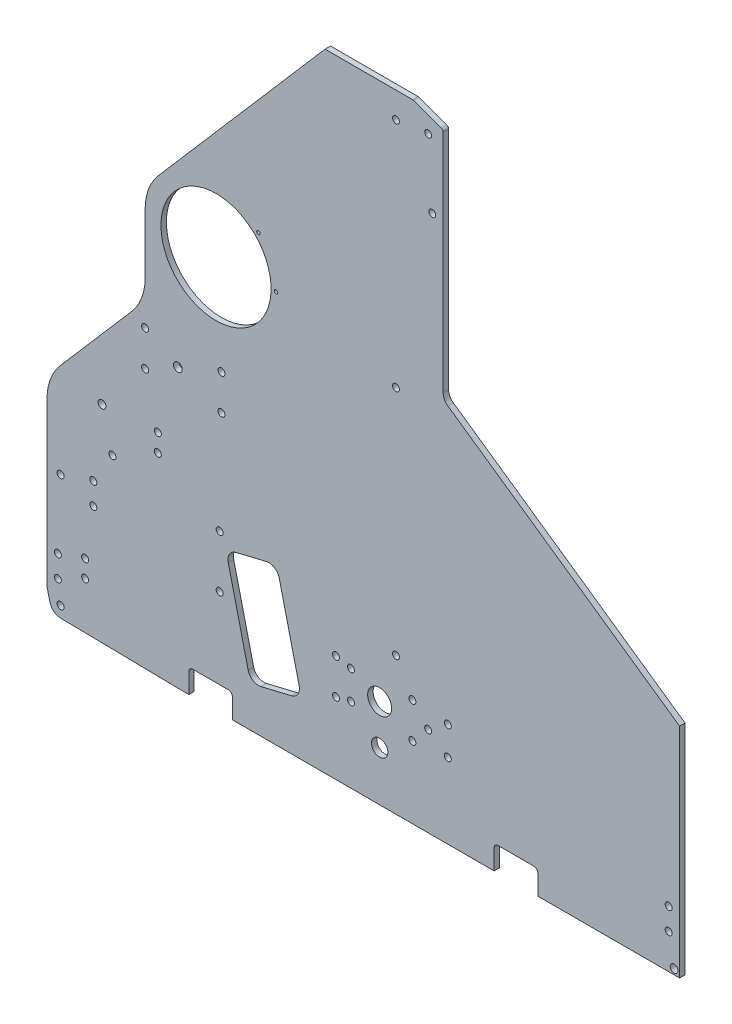
SolidWorks part; units mm, degrees
ref_plane "Front Plane" through (0, 0, 0) normal (0, 0, 1) x (1, 0, 0)
ref_plane "Top Plane" through (0, 0, 0) normal (0, 1, 0) x (1, 0, 0)
ref_plane "Right Plane" through (0, 0, 0) normal (1, 0, 0) x (0, 0, -1)
sketch "Sketch1" plane through (0, 0, 0) normal (0, 0, 1) x (1, 0, 0)
  line L0 (82.55, -20.32) -> (82.55, -6.35)
  line L2 (0, 0) -> (0, 157.48)
  line L4 (368.3, -20.32) -> (368.3, 106.68)
  line L5 (82.55, -6.35) -> (107.95, -6.35)
  line L6 (107.95, -6.35) -> (107.95, -20.32)
  line L7 (107.95, -20.32) -> (260.35, -20.32)
  line L8 (260.35, -20.32) -> (260.35, -6.35)
  line L9 (260.35, -6.35) -> (285.75, -6.35)
  line L10 (285.75, -6.35) -> (285.75, -20.32)
  line L11 (285.75, -20.32) -> (368.3, -20.32)
  line L12 (361.95, 12.7) -> (368.3, 12.7) construction
  line L13 (0, 0) -> (6.35, 0) construction
  line L14 (0.1896, -7.8901) -> (1.7771, -14.2401)
  line L15 (7.8295, -19.0491) -> (82.55, -20.32)
  line L16 (0, 0) -> (0, -6.35)
  line L17 (76.2, 141.605) -> (79.375, 141.605) construction
  line L18 (57.15, 131.2863) -> (101.6, 131.2862) construction
  line L19 (57.15, 131.2863) -> (57.15, 151.9238) construction
  line L20 (101.6, 131.2862) -> (101.6, 151.9237) construction
  line L21 (57.15, 151.9238) -> (101.6, 151.9237) construction
  line L22 (57.15, 131.2863) -> (101.6, 151.9237) construction
  line L23 (101.6, 131.2862) -> (57.15, 151.9238) construction
  line L25 (203.2, 59.805) -> (203.2, 194.805) construction
  line L26 (203.2, 194.805) -> (203.2, 329.805) construction
  line L27 (355.6, 332.105) -> (330.2, 332.105) construction
  line L28 (330.2, 332.105) -> (330.2, 217.805) construction
  line L29 (330.2, 217.805) -> (355.6, 217.805) construction
  line L30 (355.6, 217.805) -> (355.6, 332.105) construction
  line L31 (203.2, 344.805) -> (203.2, 194.805) construction
  line L32 (50.8, 332.105) -> (76.2, 332.105) construction
  line L33 (76.2, 332.105) -> (76.2, 217.805) construction
  line L34 (50.8, 217.805) -> (50.8, 332.105) construction
  line L35 (76.2, 217.805) -> (50.8, 217.805) construction
  line L36 (213.2, 344.805) -> (230.6638, 338.455)
  line L37 (203.2, 344.805) -> (161.925, 344.805)
  line L38 (203.2, 344.805) -> (213.2, 344.805)
  line L39 (348.5362, 344.805) -> (413.4623, 344.805)
  line L40 (348.5362, 344.805) -> (230.6638, 344.805) construction
  line L42 (161.925, 344.805) -> (0, 157.48)
  line L44 (230.6638, 338.455) -> (230.6638, 202.565)
  line L45 (230.6638, 202.565) -> (368.3, 106.68)
  line L46 (213.2, 344.805) -> (-141.0713, 344.805) construction
  circle A0 centre (6.35, 0) radius 2.032
  circle A1 centre (6.35, 12.7) radius 2.032
  circle A2 centre (361.95, 0) radius 2.032
  circle A3 centre (361.95, 12.7) radius 2.032
  arc A5 (1.7771, -14.2401) -> (7.8295, -19.0491) centre (7.9375, -12.7) ccw
  circle A6 centre (7.9375, -12.7) radius 2.032
  arc A7 (0, -6.35) -> (0.1896, -7.8901) centre (6.35, -6.35) ccw
  circle A8 centre (38.1, 78.105) radius 2.032
  circle A9 centre (76.2, 141.605) radius 2.54
  circle A10 centre (101.6, 131.2862) radius 2.032
  circle A11 centre (101.6, 151.9237) radius 2.032
  circle A12 centre (57.15, 151.9238) radius 2.032
  circle A13 centre (57.15, 131.2863) radius 2.032
  circle A15 centre (203.2, 59.805) radius 2
  circle A16 centre (203.2, 194.805) radius 2
  circle A17 centre (203.2, 329.805) radius 2
  circle A18 centre (63.5, 313.055) radius 2.032
  circle A20 centre (355.6, 332.105) radius 2.032
  circle A21 centre (330.2, 332.105) radius 2.032
  circle A22 centre (355.6, 217.805) radius 2.032
  circle A23 centre (330.2, 217.805) radius 2.032
  circle A24 centre (50.8, 332.105) radius 2.032
  circle A25 centre (76.2, 332.105) radius 2.032
  circle A26 centre (50.8, 217.805) radius 2.032
  circle A27 centre (76.2, 217.805) radius 2.032
  circle A28 centre (221.9319, 332.105) radius 2
  circle A29 centre (224.3138, 293.243) radius 2.032
  point P82 (203.2, 344.805)
  point P83 (221.9319, 341.63)
  dimension "D6" = 4.064
  dimension "D10" = 6.35
  dimension "D11" = 4.064
  dimension "D17" = 38.1
  dimension "D27" = 4
  dimension "D31" = 4.064
  dimension "D32" = 41.275
  dimension "D36" = 4.064
  dimension "D47" = 45.212
  dimension "D48" = 4.064
  dimension "D25" = 5.08
  dimension "D2" = 127
  dimension "D3" = 13.97
  dimension "D4" = 25.4
  dimension "D5" = 152.4
  dimension "D7" = 12.7
  dimension "D8" = 6.35
  dimension "D9" = 20.32
  dimension "D12" = 12.7
  dimension "D13" = 1.5875
  dimension "D14" = 82.55
  dimension "D15" = 368.3
  dimension "D16" = 6.35
  dimension "D18" = 98.425
  dimension "D19" = 38.1
  dimension "D20" = 63.5
  dimension "D21" = 3.175
  dimension "D22" = 270
  dimension "D23" = 20.6375
  dimension "D24" = 44.45
  dimension "D28" = 135
  dimension "D29" = 12.7
  dimension "D30" = 15
  dimension "D33" = 63.5
  dimension "D34" = 27.4638
  dimension "D37" = 114.3
  dimension "D38" = 25.4
  dimension "D39" = 12.7
  dimension "D40" = 157.48
  dimension "D41" = 142.24
  dimension "D42" = 365.125
  dimension "D43" = 10
  dimension "D44" = 6.35
  dimension "D45" = 31.75
  dimension "D46" = 6.35
  dimension "D49" = 6.35
  dimension "D50" = 203.2
extrude "Boss-Extrude1" add sketch "Sketch1" along normal blind 3.175 contours L16 A7 L14 A5 L15 L2 A0 A1 A6 region at (171.4043, 119.6328, 0)
fillet "Fillet1" radius 2.286 4 edges at (285.75, -6.35, 1.5875) (107.95, -6.35, 1.5875) (260.35, -6.35, 1.5875) (82.55, -6.35, 1.5875)
fillet "Fillet2" radius 6.35 1 edges at (230.6638, 202.565, 1.5875)
sketch "Sketch2" plane through (0, 0, 0) normal (0, 0, -1) x (-1, 0, 0)
  circle A0 centre (-100.5528, 71.086) radius 2.032 construction
  circle A1 centre (-100.5528, 40.606) radius 2.032 construction
  circle A2 centre (-22.225, 18.2025) radius 2.032 construction
  circle A3 centre (-22.225, 8.0425) radius 2.032 construction
  circle A4 centre (-100.5528, 71.086) radius 2.032
  circle A5 centre (-100.5528, 40.606) radius 2.032
  circle A6 centre (-22.225, 18.2025) radius 2.032
  circle A7 centre (-22.225, 8.0425) radius 2.032
extrude "Cut-Extrude1" cut sketch "Sketch2" against normal through all
fillet "Fillet3" radius 1.5875 2 edges at (230.6638, 338.455, 1.5875) (213.2, 344.805, 1.5875)
sketch "Sketch3" plane through (0, 0, 3.175) normal (0, 0, 1) x (1, 0, 0)
  line L0 (132.9524, 63.2646) -> (132.7215, 64.2281) construction
  line L1 (128.3814, 66.8897) -> (110.6828, 62.6472) construction
  line L2 (114.5132, 58.4237) -> (126.8822, 61.3887) construction
  line L3 (108.0212, 58.3071) -> (108.2522, 57.3436) construction
  line L4 (131.2006, 57.703) -> (140.0164, 20.9265) construction
  line L5 (144.0993, 16.7636) -> (132.9524, 63.2646) construction
  line L6 (108.2522, 57.3436) -> (119.3991, 10.8426) construction
  line L7 (121.1509, 16.4042) -> (112.3351, 53.1807) construction
  line L8 (119.3991, 10.8426) -> (119.6301, 9.8791) construction
  line L9 (144.3303, 15.8001) -> (144.0993, 16.7636) construction
  line L10 (137.8383, 15.6835) -> (125.4694, 12.7185) construction
  line L11 (123.9701, 7.2175) -> (141.6687, 11.4601) construction
  line L12 (132.9524, 63.2646) -> (132.7215, 64.2281)
  line L13 (128.3814, 66.8897) -> (110.6828, 62.6472)
  line L14 (114.5132, 58.4237) -> (126.8822, 61.3887)
  line L15 (108.0212, 58.3071) -> (108.2522, 57.3436)
  line L16 (131.2006, 57.703) -> (140.0164, 20.9265)
  line L17 (144.0993, 16.7636) -> (132.9524, 63.2646)
  line L18 (108.2522, 57.3436) -> (119.3991, 10.8426)
  line L19 (121.1509, 16.4042) -> (112.3351, 53.1807)
  line L20 (119.3991, 10.8426) -> (119.6301, 9.8791)
  line L21 (144.3303, 15.8001) -> (144.0993, 16.7636)
  line L22 (137.8383, 15.6835) -> (125.4694, 12.7185)
  line L23 (123.9701, 7.2175) -> (141.6687, 11.4601)
  line L24 (127.7894, 69.3598) -> (110.0908, 65.1172)
  line L25 (105.5512, 57.715) -> (105.7822, 56.7515)
  line L26 (105.7822, 56.7515) -> (116.9291, 10.2505)
  line L27 (116.9291, 10.2505) -> (117.16, 9.287)
  line L28 (124.5622, 4.7475) -> (142.2608, 8.99)
  line L29 (146.8003, 16.3922) -> (146.5694, 17.3557)
  line L30 (146.5694, 17.3557) -> (135.4225, 63.8567)
  line L31 (135.4225, 63.8567) -> (135.1915, 64.8202)
  line L32 (14.605, -0.1369) -> (103.7278, 32.3011) construction
  line L33 (14.605, -0.1369) -> (103.7278, 32.3011)
  line L35 (-39.6666, 74.7152) -> (103.7278, 126.9065) construction
  arc A0 (132.7215, 64.2281) -> (128.6308, 66.9403) centre (129.2206, 63.3889) ccw construction
  arc A1 (110.6828, 62.6472) -> (110.4377, 62.5791) centre (111.522, 59.1463) ccw construction
  arc A2 (128.6308, 66.9403) -> (128.3814, 66.8897) centre (129.2206, 63.3889) ccw construction
  arc A3 (110.4377, 62.5791) -> (108.0212, 58.3071) centre (111.522, 59.1463) ccw construction
  arc A4 (119.6301, 9.8791) -> (123.7207, 7.1669) centre (123.1309, 10.7183) ccw construction
  arc A5 (141.9139, 11.5281) -> (144.3303, 15.8001) centre (140.8295, 14.9609) ccw construction
  arc A6 (141.6687, 11.4601) -> (141.9139, 11.5281) centre (140.8295, 14.9609) ccw construction
  arc A7 (123.7207, 7.1669) -> (123.9701, 7.2175) centre (123.1309, 10.7183) ccw construction
  arc A8 (132.7215, 64.2281) -> (128.6308, 66.9403) centre (129.2206, 63.3889) ccw
  arc A9 (110.6828, 62.6472) -> (110.4377, 62.5791) centre (111.522, 59.1463) ccw
  arc A10 (128.6308, 66.9403) -> (128.3814, 66.8897) centre (129.2206, 63.3889) ccw
  arc A11 (110.4377, 62.5791) -> (108.0212, 58.3071) centre (111.522, 59.1463) ccw
  arc A12 (119.6301, 9.8791) -> (123.7207, 7.1669) centre (123.1309, 10.7183) ccw
  arc A13 (141.9139, 11.5281) -> (144.3303, 15.8001) centre (140.8295, 14.9609) ccw
  arc A14 (141.6687, 11.4601) -> (141.9139, 11.5281) centre (140.8295, 14.9609) ccw
  arc A15 (123.7207, 7.1669) -> (123.9701, 7.2175) centre (123.1309, 10.7183) ccw
  arc A16 (110.0908, 65.1172) -> (109.6726, 65.0012) centre (111.522, 59.1463) ccw
  arc A17 (109.6726, 65.0012) -> (105.5512, 57.715) centre (111.522, 59.1463) ccw
  arc A18 (117.16, 9.287) -> (124.1369, 4.6613) centre (123.1309, 10.7183) ccw
  arc A19 (124.1369, 4.6613) -> (124.5622, 4.7475) centre (123.1309, 10.7183) ccw
  arc A20 (142.2608, 8.99) -> (142.6789, 9.1061) centre (140.8295, 14.9609) ccw
  arc A21 (142.6789, 9.1061) -> (146.8003, 16.3922) centre (140.8295, 14.9609) ccw
  arc A22 (135.1915, 64.8202) -> (128.2147, 69.446) centre (129.2206, 63.3889) ccw
  arc A23 (128.2147, 69.446) -> (127.7894, 69.3598) centre (129.2206, 63.3889) ccw
  circle A24 centre (64.5259, 102.9405) radius 2.032 construction
  circle A25 centre (64.5259, 92.5258) radius 2.032 construction
  circle A26 centre (133.35, 208.2281) radius 1.016 construction
  circle A33 centre (26.9875, 46.9531) radius 2.032
  circle A34 centre (26.9875, 59.6531) radius 2.032
  circle A35 centre (7.9375, 53.3031) radius 2.032
  circle A36 centre (7.9375, 53.3031) radius 2.032 construction
  circle A37 centre (32.0306, 100.8109) radius 31.75 construction
  circle A38 centre (32.0306, 100.8109) radius 2.286
  circle A39 centre (123.1207, 232.9238) radius 1.016 construction
  circle A40 centre (64.5259, 102.9405) radius 2.032
  circle A41 centre (64.5259, 92.5258) radius 2.032
  circle A42 centre (133.35, 208.2281) radius 1.016
  circle A43 centre (123.1207, 232.9238) radius 1.016
  circle A44 centre (26.9875, 59.6531) radius 2.032 construction
  circle A45 centre (26.9875, 46.9531) radius 2.032 construction
  ellipse E0 centre (124.5974, 48.8487) end of major axis (128.5376, 61.3578) minor radius 6 (131.2006, 57.703) -> (126.8822, 61.3887) ccw construction
  ellipse E1 centre (122.2349, 48.2824) end of major axis (113.0518, 57.6456) minor radius 6 (114.5132, 58.4237) -> (112.3351, 53.1807) ccw construction
  ellipse E2 centre (127.7541, 25.2585) end of major axis (131.6942, 37.7675) minor radius 6 (121.1509, 16.4042) -> (125.4694, 12.7185) ccw construction
  ellipse E3 centre (130.1166, 25.8248) end of major axis (139.2998, 16.4616) minor radius 6 (137.8383, 15.6835) -> (140.0164, 20.9265) ccw construction
  ellipse E4 centre (124.5974, 48.8487) end of major axis (120.6573, 36.3397) minor radius 6 (131.2006, 57.703) -> (126.8822, 61.3887) ccw
  ellipse E5 centre (122.2349, 48.2824) end of major axis (131.4181, 38.9192) minor radius 6 (114.5132, 58.4237) -> (112.3351, 53.1807) ccw
  ellipse E6 centre (127.7541, 25.2585) end of major axis (131.6942, 37.7675) minor radius 6 (121.1509, 16.4042) -> (125.4694, 12.7185) ccw
  ellipse E7 centre (130.1166, 25.8248) end of major axis (139.2998, 16.4616) minor radius 6 (137.8383, 15.6835) -> (140.0164, 20.9265) ccw
  point P115 (32.0306, 100.8109)
  dimension "D3" = 63.5
  dimension "D4" = 4.572
  dimension "D2" = 88.9
  dimension "D1" = 2.54
extrude "Cut-Extrude2" cut sketch "Sketch3" against normal through all contours A22 A23 L24 A16 A17 L25 L26 L27 A18 A19 L28 A20 A21 L29 L30 L31 A15 A12 L20 L18 L15 A11 A9 L13 A10 A8 L12 L17 L21 A13 A14 L23 | A12 A15 L23 A14 A13 L21 L17 L12 A8 A10 L13 A9 A11 L15 L18 L20 E7 L22 E6 L19 E5 L14 E4 L16 | L22 E7 L16 E4 L14 E5 L19 E6 | A38 | A41 | A40 | A35 | A34 | A33 | A43 | A42 region at (137.844, 39.8506, 3.175) region at (126.1758, 37.0536, 3.175) region at (128.1544, 68.6507, 3.175) region at (32.0306, 100.8109, 3.175) region at (64.5259, 102.9405, 3.175) region at (64.5259, 92.5258, 3.175)
sketch "Sketch4" plane through (0, 0, 3.175) normal (0, 0, 1) x (1, 0, 0)
  line L0 (57.15, 151.9238) -> (101.6, 151.9237) construction
  line L1 (168.275, 21.4312) -> (212.725, 21.4312) construction
  line L2 (168.275, 21.4312) -> (168.275, 42.0687) construction
  line L3 (168.275, 42.0687) -> (212.725, 42.0687) construction
  line L4 (212.725, 21.4312) -> (212.725, 42.0687) construction
  line L5 (168.275, 21.4312) -> (212.725, 42.0687) construction
  line L6 (168.275, 42.0687) -> (212.725, 21.4312) construction
  line L7 (57.15, 131.2863) -> (57.15, 151.9238) construction
  line L8 (107.95, -20.32) -> (260.35, -20.32) construction
  line L9 (193.675, 31.75) -> (177.005, 31.75) construction
  line L10 (190.5, 31.75) -> (193.675, 31.75) construction
  line L11 (6.35, 12.7) -> (361.95, 12.7) construction
  line L12 (107.95, -6.35) -> (107.95, -20.32) construction
  line L13 (193.675, 31.75) -> (220.6625, 31.75) construction
  line L14 (177.005, 23.4569) -> (177.005, 40.0431) construction
  line L15 (213.2, 44.805) -> (193.2, 44.805) construction
  line L16 (213.2, 44.805) -> (213.2, 344.805) construction
  line L17 (213.2, 344.805) -> (193.2, 344.805) construction
  line L18 (193.2, 44.805) -> (193.2, 344.805) construction
  line L19 (213.2, 44.805) -> (193.2, 344.805) construction
  line L20 (213.2, 344.805) -> (193.2, 44.805) construction
  line L21 (226.9319, 332.105) -> (226.9319, 31.75) construction
  line L22 (237.33, 40.0431) -> (233.3612, 40.0431) construction
  line L23 (237.33, 23.4569) -> (233.3612, 23.4569) construction
  circle A0 centre (168.275, 42.0687) radius 2.032
  circle A1 centre (212.725, 42.0687) radius 2.032
  circle A2 centre (212.725, 21.4312) radius 2.032
  circle A3 centre (168.275, 21.4312) radius 2.032
  circle A4 centre (193.675, 31.75) radius 6.985
  circle A7 centre (220.6625, 31.75) radius 14.2875 construction
  circle A8 centre (193.675, 31.75) radius 12.7 construction
  circle A9 centre (177.005, 40.0431) radius 2.032
  circle A10 centre (177.005, 23.4569) radius 2.032
  circle A11 centre (237.33, 40.0431) radius 2.032 construction
  circle A12 centre (237.33, 23.4569) radius 2.032 construction
  circle A13 centre (193.675, 8.4667) radius 4.7625
  circle A14 centre (221.9319, 31.75) radius 2.032
  circle A15 centre (221.9319, 31.75) radius 5 construction
  circle A16 centre (221.9319, 332.105) radius 5 construction
  circle A17 centre (233.3612, 23.4569) radius 2.032
  circle A18 centre (233.3612, 40.0431) radius 2.032
  point P0 (190.5, 31.75)
  point P26 (203.2, 194.805)
  point P38 (177.005, 31.75)
  dimension "D1" = 4.064
  dimension "D4" = 13.97
  dimension "D7" = 9.525
  dimension "D10" = 25.4
  dimension "D11" = 28.575
  dimension "D16" = 10
  dimension "D17" = 4.064
  dimension "D18" = 10
  dimension "D2" = 52.07
  dimension "D3" = 3.175
  dimension "D5" = 82.55
  dimension "D6" = 26.9875
  dimension "D8" = 20
  dimension "D9" = 300
  dimension "D12" = 16.67
  dimension "D13" = 16.5862
  dimension "D14" = 60.325
  dimension "D15" = 23.2833
  dimension "D19" = 3.9688
extrude "Cut-Extrude3" cut sketch "Sketch4" against normal through all
sketch "Sketch5" plane through (0, 0, -187.325) normal (0, 0, -1) x (-1, 0, 0)
  line L0 (-57.15, 223.5947) -> (-57.15, 165.3337)
  line L1 (-161.925, 344.805) -> (-52.7201, 218.4699) construction
  line L2 (-57.15, 165.3337) -> (0, 99.219)
  line L3 (0, -6.35) -> (0, 157.48) construction
  line L4 (-50.4199, 215.8089) -> (0, 157.48) construction
  line L5 (-50.4199, 215.8089) -> (0, 157.48) construction
  line L6 (-57.15, 223.5947) -> (0, 157.48)
  line L7 (0, 157.48) -> (0, 99.219)
  circle A0 centre (-98.425, 208.2281) radius 32.0675
  circle A1 centre (-365.125, -17.145) radius 2.286 construction
  circle A2 centre (-365.125, -17.145) radius 2.286
  dimension "D3" = 64.135
  dimension "D1" = 38.1
  dimension "D2" = 57.15
  dimension "D4" = 41.275
  dimension "D5" = 41.275
extrude "Cut-Extrude5" cut sketch "Sketch5" against normal through all contours A0 | L7 L6 L0 L2 | A2 region at (28.575, 161.4068, -187.325) region at (98.425, 208.2281, -187.325)
fillet "Fillet4" radius 31.75 3 edges at (0, 99.219, 1.5875) (57.15, 165.3337, 1.5875) (57.15, 223.5947, 1.5875)
